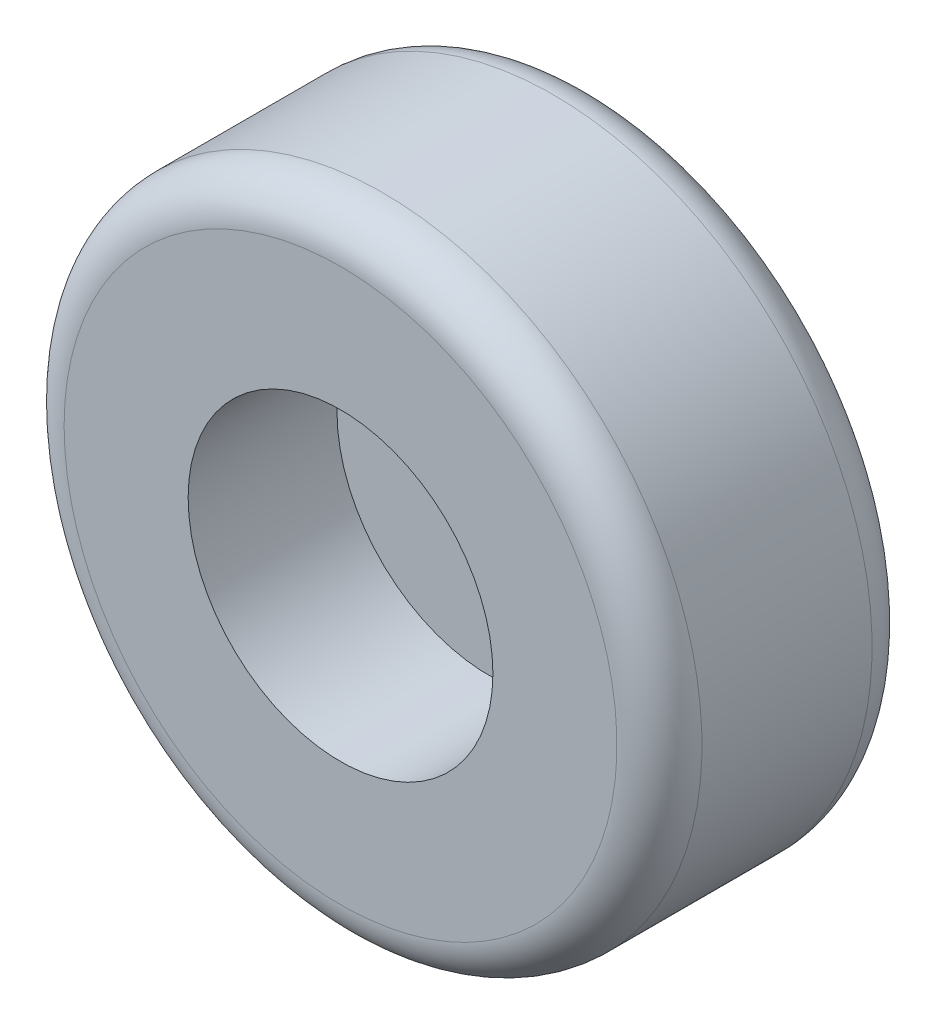
SolidWorks part; units mm, degrees
material "Rubber"
ref_plane "Front Plane" through (0, 0, 0) normal (0, 0, 1) x (1, 0, 0)
ref_plane "Top Plane" through (0, 0, 0) normal (0, 1, 0) x (1, 0, 0)
ref_plane "Right Plane" through (0, 0, 0) normal (1, 0, 0) x (0, 0, -1)
sketch "Sketch1" plane through (0, 0, 0) normal (0, 1, 0) x (1, 0, 0)
  line L0 (0, 41.849) -> (0, -41.2616) construction
  line L2 (0, 0) -> (19.5, 0)
  line L3 (0, 0) -> (0, -7.5)
  line L4 (10.75, -18) -> (19.5, -18)
  line L5 (22.5, -3) -> (22.5, -15)
  line L6 (0, -7.5) -> (10.75, -7.5)
  line L9 (10.75, -7.5) -> (10.75, -18)
  arc A0 (19.5, -18) -> (22.5, -15) centre (19.5, -15) ccw
  arc A1 (19.5, 0) -> (22.5, -3) centre (19.5, -3) cw
  dimension "D1" = 3
  dimension "D2" = 18
  dimension "D3" = 45
  dimension "D4" = 7.5
  dimension "D5" = 21.5
revolve "Revolve1" add sketch "Sketch1" angle 360 about L0
ref_axis "AX-SHAFT" through (0, 0, -0.9) along (0, 0, 1)
sketch "Sketch2" plane through (0, 0, 0) normal (0, 0, 1) x (1, 0, 0)
  line L0 (-1.118, 1) -> (1.118, 1)
  line L1 (0, -1.5) -> (-2.385, -1.5) construction
  arc A0 (-1.118, 1) -> (1.118, 1) centre (0, 0) ccw
  dimension "D1" = 3
  dimension "D2" = 2.5
extrude "Cut-Extrude1" cut sketch "Sketch2" along normal through all
